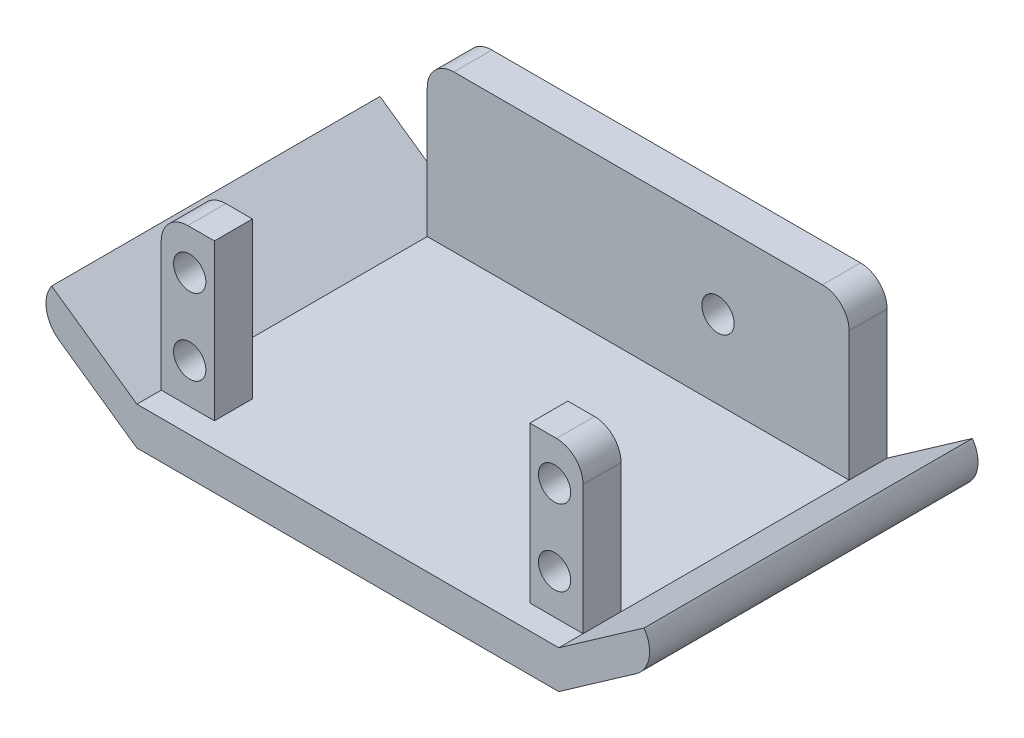
SolidWorks part; units mm, degrees
ref_plane "Front" through (0, 0, 0) normal (0, 0, 1) x (1, 0, 0)
ref_plane "Top" through (0, 0, 0) normal (0, 1, 0) x (1, 0, 0)
ref_plane "Right" through (0, 0, 0) normal (1, 0, 0) x (0, 0, -1)
sketch "Sketch1" plane through (0, 0, 0) normal (0, 1, 0) x (1, 0, 0)
  line L1 (0, 0) -> (55.5, 0)
  line L2 (0, 0) -> (0, 43.2)
  line L3 (0, 43.2) -> (55.5, 43.2)
  line L4 (55.5, 0) -> (55.5, 43.2)
  dimension "D1" = 55.5
  dimension "D2" = 43.2
extrude "base" add sketch "Sketch1" along normal blind 5
sketch "Sketch2" plane through (0, 0, -43.2) normal (0, 0, -1) x (-1, 0, 0)
  line L1 (0, 5) -> (0, 0) construction
  line L2 (-55.5, 0) -> (0, 0)
  line L3 (-55.5, 0) -> (-55.5, 25.5)
  line L4 (-55.5, 25.5) -> (0, 25.5)
  line L5 (0, 0) -> (0, 25.5)
  line L6 (-55.5, 5) -> (0, 5) construction
  dimension "D1" = 20.5
extrude "wall" add sketch "Sketch2" against normal blind 5
ref_plane "Plane1" through (0, 0, -8.2) normal (0, 0, 1) x (1, 0, 0)
sketch "Sketch3" plane through (0, 0, -8.2) normal (0, 0, 1) x (1, 0, 0)
  line L0 (0, 5) -> (55.5, 5) construction
  line L1 (0, 25.5) -> (7, 25.5)
  line L2 (0, 25.5) -> (0, 5)
  line L3 (0, 5) -> (7, 5)
  line L4 (7, 25.5) -> (7, 5)
  line L5 (27.75, 5) -> (27.75, 25.5) construction
  line L6 (55.5, 5) -> (0, 5) construction
  line L7 (0, 25.5) -> (55.5, 25.5) construction
  line L8 (55.5, 5) -> (48.5, 5)
  line L9 (48.5, 25.5) -> (48.5, 5)
  line L10 (55.5, 25.5) -> (48.5, 25.5)
  line L11 (55.5, 25.5) -> (55.5, 5)
  dimension "D1" = 7
extrude "mountingTabs" add sketch "Sketch3" along normal blind 5
sketch "Sketch4" plane through (0, 0, 0) normal (0, 0, 1) x (1, 0, 0)
  line L0 (27.75, 0) -> (27.75, 25.5) construction
  line L1 (0, 0) -> (55.5, 0) construction
  line L2 (0, 25.5) -> (55.5, 25.5) construction
  line L3 (0, 0) -> (-10.2089, 7.1483)
  line L4 (0, 5) -> (-11.2182, 12.8551)
  line L5 (0, 5) -> (0, 0)
  line L6 (55.5, 5) -> (66.7182, 12.8551)
  line L7 (55.5, 5) -> (55.5, 0)
  line L8 (55.5, 0) -> (65.7089, 7.1483)
  arc A0 (-11.2182, 12.8551) -> (-10.2089, 7.1483) centre (-7.8572, 10.5069) ccw
  arc A1 (66.7182, 12.8551) -> (65.7089, 7.1483) centre (63.3572, 10.5069) cw
  dimension "D1" = 145
  dimension "D2" = 12.4627
  dimension "D3" = 13.6949
extrude "lips" add sketch "Sketch4" against normal up to surface (43.2 mm away) up to face at (27.75, 12.75, -43.2)
sketch "Sketch5" plane through (0, 0, -3.2) normal (0, 0, 1) x (1, 0, 0)
  line L0 (27.75, 0) -> (27.75, 25.5) construction
  line L3 (0, 15.25) -> (55.5, 15.25) construction
  line L4 (0, 25.5) -> (0, 5) construction
  line L5 (55.5, 5) -> (55.5, 25.5) construction
  line L6 (7, 25.5) -> (0, 25.5) construction
  line L7 (0, 0) -> (55.5, 0) construction
  line L8 (0, 25.5) -> (55.5, 25.5) construction
  circle A0 centre (3.75, 20.25) radius 2.125
  circle A1 centre (3.75, 10.25) radius 2.125
  circle A4 centre (51.75, 10.25) radius 2.125
  circle A5 centre (51.75, 20.25) radius 2.125
  dimension "D1" = 4.25
  dimension "D2" = 5.25
  dimension "D3" = 3.75
extrude "mountingHoles" cut sketch "Sketch5" against normal blind 5
fillet "fillets" radius 3.5 4 edges at (55.5, 25.5, -40.7) (55.5, 25.5, -5.7) (0, 25.5, -40.7) (0, 25.5, -5.7)
sketch "Sketch6" plane through (0, 0, -38.2) normal (0, 0, 1) x (1, 0, 0)
  line L0 (3.5, 25.5) -> (52, 25.5) construction
  line L1 (55.5, 5) -> (55.5, 22) construction
  circle A0 centre (38.25, 15.25) radius 2.125
  dimension "D1" = 4.25
  dimension "D2" = 10.25
  dimension "D3" = 17.25
extrude "throughHole" cut sketch "Sketch6" against normal blind 5
